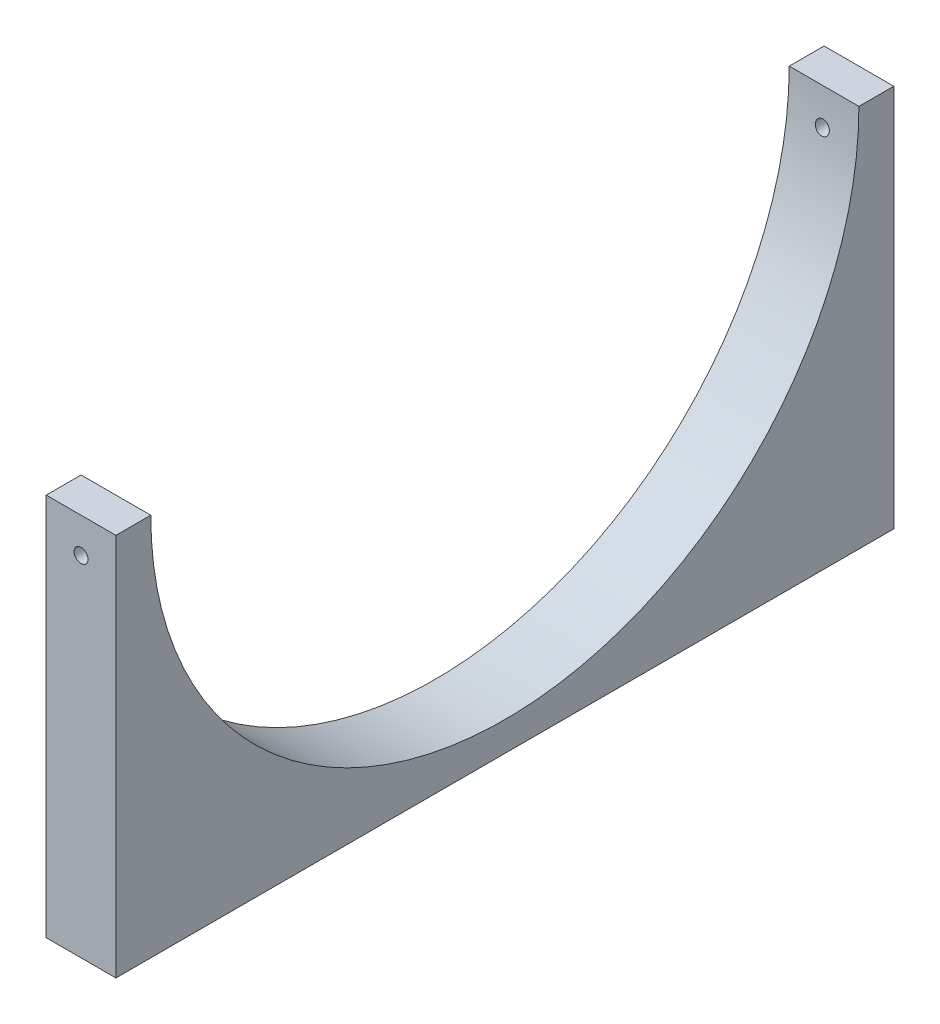
SolidWorks part; units mm, degrees
material "1060 Alloy"
ref_plane "Front Plane" through (0, 0, 0) normal (0, 0, 1) x (1, 0, 0)
ref_plane "Top Plane" through (0, 0, 0) normal (0, 1, 0) x (1, 0, 0)
ref_plane "Right Plane" through (0, 0, 0) normal (1, 0, 0) x (0, 0, -1)
sketch "Sketch1" plane through (0, 0, 0) normal (0, 1, 0) x (1, 0, 0)
  line L1 (-68.4091, -57.85) -> (121.0909, -57.85)
  line L2 (-68.4091, -57.85) -> (-68.4091, 53.75)
  line L3 (-68.4091, 53.75) -> (121.0909, 53.75)
  line L4 (121.0909, -57.85) -> (121.0909, 53.75)
  dimension "D1" = 111.6
  dimension "D2" = 189.5
extrude "Boss-Extrude1" add sketch "Sketch1" along normal blind 80
sketch "Sketch3" plane through (0, 0, 57.85) normal (0, 0, 1) x (1, 0, 0)
  line L0 (-68.4091, 0) -> (121.0909, 0) construction
  line L1 (-68.4091, 80) -> (-68.4091, 0) construction
  circle A0 centre (-6.7091, 45) radius 8.15
  circle A1 centre (44.2909, 45) radius 8.15
  circle A2 centre (95.2909, 45) radius 8.15
  dimension "D1" = 16.3
  dimension "D2" = 16.3
  dimension "D3" = 16.3
  dimension "D5" = 0
  dimension "D7" = 51
  dimension "D8" = 51
  dimension "D9" = 61.7
  dimension "D4" = 45
  dimension "D6" = 0
extrude "Cut-Extrude2" cut sketch "Sketch3" against normal blind 40
sketch "Sketch4" plane through (0, 0, -53.75) normal (0, 0, -1) x (-1, 0, 0)
  line L0 (68.4091, 0) -> (-121.0909, 0) construction
  circle A0 centre (-18.7909, 45) radius 10.3
  circle A1 centre (-44.2909, 45) radius 8.15 construction
  dimension "D1" = 20.6
  dimension "D2" = 25.5
  dimension "D3" = 45
extrude "Cut-Extrude3" cut sketch "Sketch4" against normal blind 40
sketch "Sketch2" plane through (-68.4091, 0, 0) normal (-1, 0, 0) x (0, 0, 1)
  line L0 (57.85, 80) -> (57.85, 0) construction
  line L1 (-53.75, 0) -> (57.85, 0) construction
  line L2 (-101.4382, 55) -> (76.5005, 55)
  line L3 (-48.75, 55) -> (52.85, 55)
  line L4 (-48.75, 55) -> (-48.75, 118.783)
  line L5 (-48.75, 118.783) -> (52.85, 118.783)
  line L6 (52.85, 55) -> (52.85, 118.783)
  line L7 (-91.5671, 45) -> (56.581, 45)
  circle A0 centre (2.05, 55) radius 50.8
  line M2 (57.85, 0) -> (57.85, 80)
  line M3 (57.85, 80) -> (-53.75, 80)
  line M4 (-53.75, 80) -> (-53.75, 0)
  dimension "D1" = 101.6
  dimension "D2" = 55.8
  dimension "D3" = 55
  dimension "D4" = 101.6
  dimension "D5" = 10
extrude "Cut-Extrude1" cut sketch "Sketch2" against normal through all contours L2 A0 M3 | A0 L4 M3 | L2 A0 | A0 L6 M3 | L2 L4 M3 M4 | L6 L2 M2 M3 | L7 A0 region at (-68.4091, 67.2225, 2.05) region at (-68.4091, 67.5, -51.25) region at (-68.4091, 73.8338, -46.8008) region at (-68.4091, 50.0164, 2.05) region at (-68.4091, 67.5, 55.35) region at (-68.4091, 73.8338, 50.9008) region at (-68.4091, 27.9434, 2.05)
sketch "Sketch5" plane through (-68.4091, 0, 0) normal (-1, 0, 0) x (0, 0, 1)
  circle A0 centre (5.8994, 41.151) radius 83.6376
  point P2 (5.8994, 41.151)
extrude "Cut-Extrude5" cut sketch "Sketch5" against normal through all from offset 10 offset against normal yes
sketch "Sketch6" plane through (0, 0, 0) normal (0, -1, 0) x (1, 0, 0)
  line L0 (-58.4091, 57.85) -> (-58.4091, -53.75) construction
  line L1 (-68.4091, 57.85) -> (-58.4091, 57.85) construction
  line L2 (-58.4091, -53.75) -> (-68.4091, -53.75) construction
  circle A0 centre (-63.4091, 42.85) radius 2
  circle A1 centre (-63.4091, -38.75) radius 2
  dimension "D1" = 4
  dimension "D2" = 4
  dimension "D6" = 15
  dimension "D3" = 5
  dimension "D4" = 5
  dimension "D5" = 15
extrude "Cut-Extrude6" cut sketch "Sketch6" against normal blind 15
sketch "Sketch7" plane through (0, 0, 57.85) normal (0, 0, 1) x (1, 0, 0)
  line L0 (-58.4091, 0) -> (-58.4091, 55) construction
  line L1 (-58.4091, 55) -> (-68.4091, 55) construction
  circle A0 centre (-63.4091, 50) radius 1
  dimension "D1" = 2
  dimension "D2" = 5
  dimension "D3" = 5
extrude "Cut-Extrude7" cut sketch "Sketch7" against normal through all both and the other way through all
